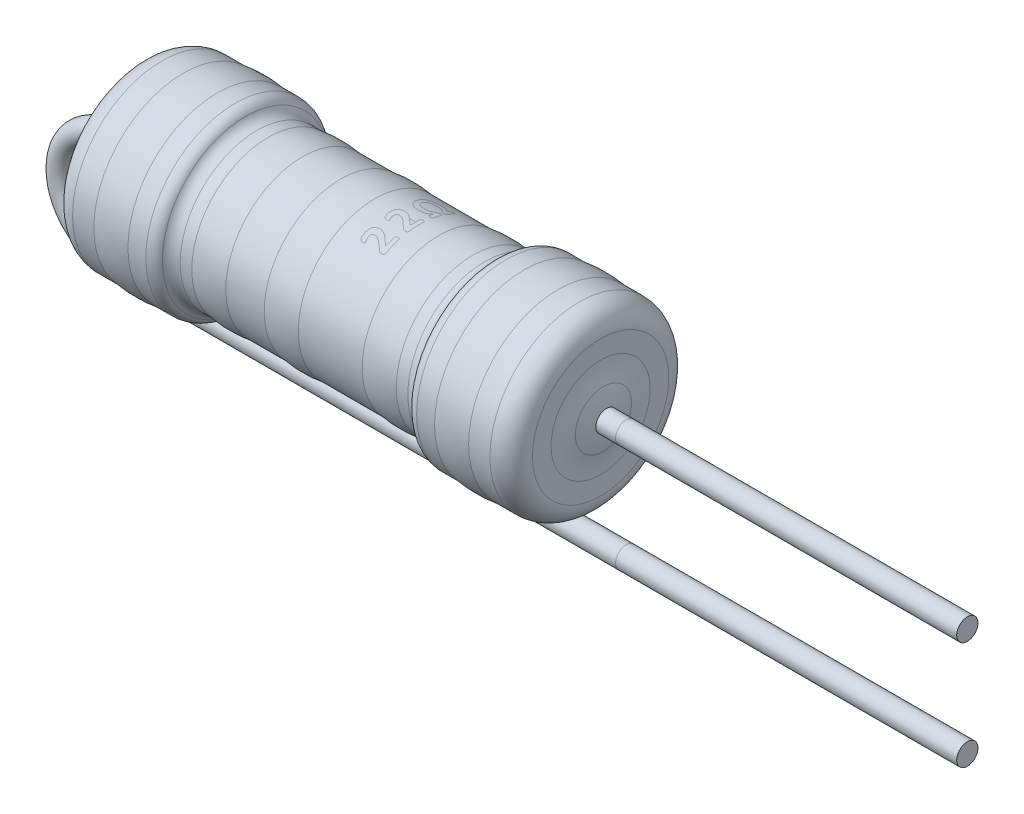
SolidWorks part; units mm, degrees
ref_plane "Front Plane" through (0, 0, 0) normal (0, 0, 1) x (1, 0, 0)
ref_plane "Top Plane" through (0, 0, 0) normal (0, 1, 0) x (1, 0, 0)
ref_plane "Right Plane" through (0, 0, 0) normal (1, 0, 0) x (0, 0, -1)
sketch "Sketch Set Wire Width" plane through (0, 0, 0) normal (0, 0, 1) x (1, 0, 0)
  line L0 (0, 0) -> (6, 0)
  line L1 (6, -2.54) -> (-6, -2.54)
  line L2 (6, 0) -> (14.0102, 0)
  line L3 (-6, 0) -> (-6, -2.54) construction
  line L4 (-6, 0) -> (-6, -2.54) construction
  line L5 (6, -2.54) -> (6, 0) construction
  line L6 (6, -2.54) -> (14.0102, -2.54)
  line L7 (14.0102, -2.54) -> (14.0102, 0) construction
  line L8 (-6, 0) -> (0, 0)
  arc A0 (-6, 0) -> (-6, -2.54) centre (-6, -1.27) ccw
  dimension "D2" = 2.54
  dimension "D3" = 30
  dimension "D1" = 12
  dimension "D4" = 6
sketch "Sketch Wire Diameter" plane through (0, 0, 0) normal (1, 0, 0) x (0, 0, -1)
  circle A0 centre (0, 0) radius 0.25
  dimension "D1" = 0.5
sweep "SET WIRE LENGTH" add profiles "Sketch Wire Diameter" path "Sketch Set Wire Width"
sketch "Sketch3" plane through (0, 0, 0) normal (0, 0, 1) x (1, 0, 0)
  line L0 (-5.4, 0) -> (5.4, 0)
  line L1 (0, 0) -> (0, 1.8) construction
  line L2 (-2.9, 1.8) -> (2.9, 1.8)
  line L3 (-5.4, 0) -> (-5.4, 1.6)
  line L4 (-4.9, 2.1) -> (-3.18, 2.1)
  line L5 (-2.9, 1.82) -> (-2.9, 1.8)
  line L6 (5.4, 0) -> (5.4, 1.6)
  line L7 (4.9, 2.1) -> (3.18, 2.1)
  line L8 (2.9, 1.82) -> (2.9, 1.8)
  arc A0 (-5.4, 1.6) -> (-4.9, 2.1) centre (-4.9, 1.6) cw
  arc A1 (5.4, 1.6) -> (4.9, 2.1) centre (4.9, 1.6) ccw
  arc A2 (-3.18, 2.1) -> (-2.9, 1.82) centre (-3.18, 1.82) cw
  arc A3 (3.18, 2.1) -> (2.9, 1.82) centre (3.18, 1.82) ccw
  dimension "D5" = 0.5
  dimension "D6" = 0.28
  dimension "D1" = 10.8
  dimension "D2" = 5.8
  dimension "D3" = 1.8
  dimension "D4" = 2.1
revolve "Revolve2" add sketch "Sketch3" angle 360 about L0
fillet "Fillet1" radius 0.3 2 edges at (2.9, 0, 1.8) (-2.9, 0, 1.8)
sketch "Sketch5" plane through (0, 0, 0) normal (0, 0, 1) x (1, 0, 0)
  line L0 (0, 0) -> (2, 0) construction
  line L1 (0, 0) -> (-0.3, 0) construction
  line L2 (-0.3, 0) -> (-2, 0) construction
  line L3 (-2, 0) -> (-4, 0) construction
  line L4 (2, 0) -> (4, 0) construction
  line L5 (-4, 0) -> (-4, 2.1) construction
  line L6 (-0.3, 0) -> (-0.3, 1.8) construction
  line L7 (-2, 0) -> (-2, 1.8) construction
  line L8 (2, 0) -> (2, 1.8) construction
  line L9 (4, 0) -> (4, 2.1) construction
  line L10 (-4, 2.1) -> (-4, 2.13) construction
  line L11 (-4.9, 2.1) -> (-3.18, 2.1) construction
  line L12 (4.9, 2.1) -> (3.18, 2.1) construction
  line L13 (-2.9, 1.8) -> (2.9, 1.8) construction
  line L14 (-2, 1.8) -> (-2, 1.83) construction
  line L17 (-4.4, 2.1) -> (-3.6, 2.1)
  line L19 (-5.4, 0) -> (5.4, 0) construction
  line L22 (-2.4, 1.8) -> (-1.6, 1.8) construction
  line L26 (-0.7, 1.8) -> (0.1, 1.8) construction
  line L30 (1.6, 1.8) -> (2.4, 1.8) construction
  line L34 (3.6, 2.1) -> (4.4, 2.1) construction
  line L36 (-0.3, 1.8) -> (-0.3, 1.83) construction
  line L37 (2, 1.8) -> (2, 1.83) construction
  line L38 (4, 2.1) -> (4, 2.13) construction
  arc A0 (-4.4, 2.1) -> (-3.6, 2.1) centre (-4, -0.5517) cw
  arc A1 (-2.4, 1.8) -> (-1.6, 1.8) centre (-2, -0.8517) cw construction
  arc A2 (-0.7, 1.8) -> (0.1, 1.8) centre (-0.3, -0.8517) cw construction
  arc A3 (1.6, 1.8) -> (2.4, 1.8) centre (2, -0.8517) cw construction
  arc A4 (3.6, 2.1) -> (4.4, 2.1) centre (4, -0.5517) cw construction
  dimension "D3" = 0.8
  dimension "D1" = 4
  dimension "D2" = 4
  dimension "D4" = 0.03
  dimension "D5" = 2
  dimension "D6" = 2
  dimension "D7" = 1.7
revolve "Band 1" add sketch "Sketch5" angle 360 about L2
sketch "Sketch8" plane through (0, 0, 0) normal (0, 0, 1) x (1, 0, 0)
  line L0 (-2.4, 1.8) -> (-1.6, 1.8) construction
  line L1 (-2.4, 1.8) -> (-1.6, 1.8)
  arc A0 (-1.6, 1.8) -> (-2.4, 1.8) centre (-2, -0.8517) ccw construction
  arc A1 (-1.6, 1.8) -> (-2.4, 1.8) centre (-2, -0.8517) ccw
revolve "Band 2" add sketch "Sketch8" angle 360 about L2
sketch "Sketch9" plane through (0, 0, 0) normal (0, 0, 1) x (1, 0, 0)
  line L0 (-0.7, 1.8) -> (0.1, 1.8) construction
  line L1 (-0.7, 1.8) -> (0.1, 1.8)
  arc A0 (0.1, 1.8) -> (-0.7, 1.8) centre (-0.3, -0.8517) ccw construction
  arc A1 (0.1, 1.8) -> (-0.7, 1.8) centre (-0.3, -0.8517) ccw
revolve "Band 3" add sketch "Sketch9" angle 360 about L2
sketch "Sketch10" plane through (0, 0, 0) normal (0, 0, 1) x (1, 0, 0)
  line L0 (1.6, 1.8) -> (2.4, 1.8) construction
  line L1 (1.6, 1.8) -> (2.4, 1.8)
  arc A0 (2.4, 1.8) -> (1.6, 1.8) centre (2, -0.8517) ccw construction
  arc A1 (2.4, 1.8) -> (1.6, 1.8) centre (2, -0.8517) ccw
revolve "Band 4" add sketch "Sketch10" angle 360 about L0
sketch "Sketch11" plane through (0, 0, 0) normal (0, 0, 1) x (1, 0, 0)
  line L0 (3.6, 2.1) -> (4.4, 2.1) construction
  line L1 (3.6, 2.1) -> (4.4, 2.1)
  arc A0 (4.4, 2.1) -> (3.6, 2.1) centre (4, -0.5517) ccw construction
  arc A1 (4.4, 2.1) -> (3.6, 2.1) centre (4, -0.5517) ccw
revolve "Band 5" add sketch "Sketch11" angle 360 about L4
sketch "Sketch12" plane through (0, 0, 0) normal (0, 0, 1) x (1, 0, 0)
  line L0 (-5.35, 0) -> (5.35, 0) construction
  line L1 (-5.35, 1) -> (-5.35, 0)
  line L2 (5.35, 1) -> (5.35, 0)
  line L3 (-5.35, 0) -> (-5.55, 0)
  line L4 (5.35, 0) -> (5.55, 0)
  arc A0 (-5.35, 1) -> (-5.55, 0) centre (-2.95, 0) ccw
  arc A1 (5.35, 1) -> (5.55, 0) centre (2.95, 0) cw
  dimension "D3" = 0.2
  dimension "D4" = 2.6
  dimension "D1" = 10.7
  dimension "D2" = 1
revolve "Revolve10" add sketch "Sketch12" angle 360 about L0
fillet "Fillet2" radius 2 2 edges at (5.4, 0, 0.8703) (-5.4, 0, -0.8703)
ref_plane "Plane2" through (0, 3, 0) normal (0, 1, 0) x (1, 0, 0)
sketch "Sketch13" plane through (0, 3, 0) normal (0, 1, 0) x (1, 0, 0)
  line L0 (0, 0) -> (1.15, 0) construction
  line L1 (1.15, 1.75) -> (1.15, -1.75) construction
  text T0 "22Ω" font "Calibri" height 0.6
  dimension "D1" = 3.5
  dimension "D2" = 1.15
wrap "Wrap1" sketch "Sketch13" wrap type scribe source sketch "Sketch13" face at (0.1, 1.8, 0)
